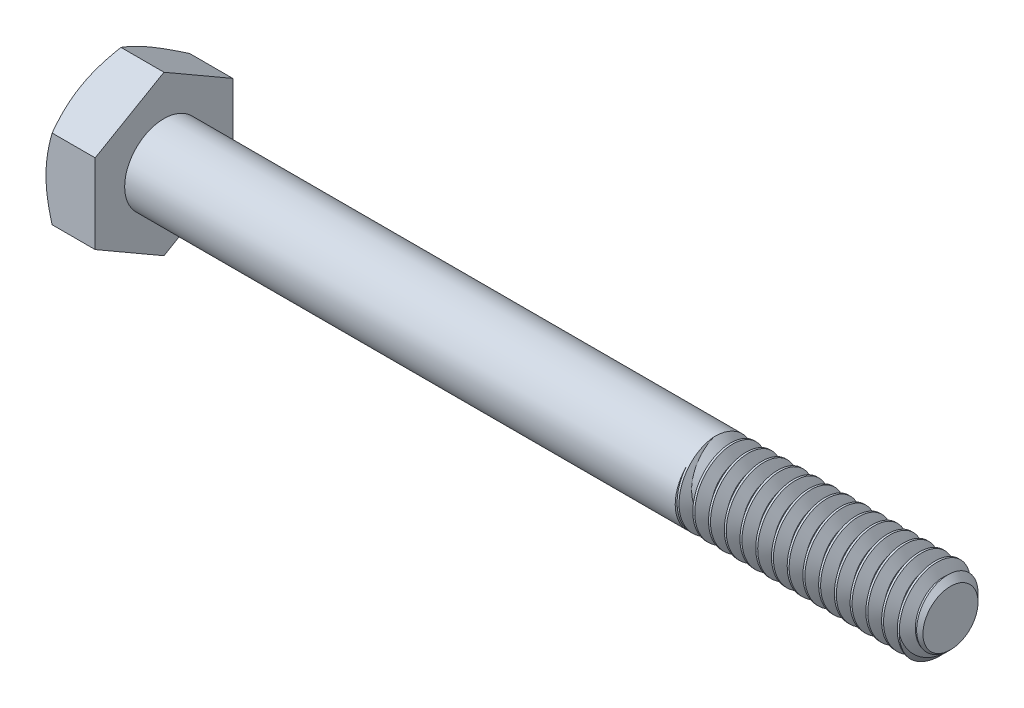
SolidWorks part; units mm, degrees
ref_plane "Front Plane" through (0, 0, 0) normal (0, 0, 1) x (1, 0, 0)
ref_plane "Top Plane" through (0, 0, 0) normal (0, 1, 0) x (1, 0, 0)
ref_plane "Right Plane" through (0, 0, 0) normal (1, 0, 0) x (0, 0, -1)
sketch "Sketch1" plane through (0, 0, 0) normal (0, 0, 1) x (1, 0, 0)
  line L0 (-33.7344, 0) -> (33.7344, 0) construction
  line L1 (33.7344, 3.175) -> (33.7344, -3.175) construction
  line L2 (-29.7656, 5.5563) -> (-29.7656, -5.5563) construction
  line L3 (-33.7344, 5.5562) -> (-33.7344, -5.5562) construction
  point P9 (-29.7656, 0)
  point P10 (29.2894, -3.175)
  dimension "Screw Dia" = 6.35
  dimension "Hex" = 11.1125
  dimension "Head Ht" = 3.9688
  dimension "Screw Lenght" = 63.5
  dimension "D1" = 4.445
ref_plane "Plane2" through (33.7344, 0, 0) normal (1, 0, 0) x (0, 0, -1)
sketch "Sketch5" plane through (33.7344, 0, 0) normal (1, 0, 0) x (0, 0, -1)
  circle A0 centre (0, 0) radius 3.175
extrude "Boss-Extrude3" add sketch "Sketch5" against normal up to vertex (63.5 mm away) up to point (-29.7656, 0, 0)
sketch "Sketch9" plane through (33.7344, 0, 0) normal (1, 0, 0) x (0, 0, -1)
  circle A1 centre (0, 0) radius 3.175
  circle A2 centre (0, 0) radius 3.175
  dimension "D1" = 0
curve "Helix/Spiral1" pitch 1.27 height 20.32 turns 16 parameters "Pitch"=1.27
chamfer "Chamfer1" distance 0.9525 angle 45 1 edges at (33.7344, 0, -3.175)
sketch "Sketch10" plane through (0, 0, 0) normal (0, 0, 1) x (1, 0, 0)
  line L0 (33.7344, 3.175) -> (34.2106, 2.3501)
  line L1 (34.2106, 2.3501) -> (34.3694, 2.3501)
  line L2 (34.3694, 2.3501) -> (34.8456, 3.175)
  line L3 (33.7344, 3.175) -> (34.8456, 3.175)
  line L4 (34.29, 3.175) -> (34.29, 2.3501) construction
  line L5 (33.9725, 2.7626) -> (34.6075, 2.7626) construction
  dimension "D1" = 60
  dimension "D2" = 0.1588
  dimension "D3" = 0.635
sweep "Cut-Sweep1" cut profiles "Sketch10" path "Helix/Spiral1" align with end faces yes
sketch "Sketch11" plane through (0, 0, 0) normal (0, 0, 1) x (1, 0, 0)
  line L0 (-29.7656, 3.175) -> (-29.7656, 0)
  line L1 (-29.7656, 0) -> (17.8594, 0)
  line L3 (17.8594, 0) -> (14.6844, 3.175)
  line L4 (-29.7656, 3.175) -> (14.6844, 3.175)
  dimension "D1" = 45
  dimension "MIn Thread" = 19.05
revolve "Revolve1" add sketch "Sketch11" angle 360 about L1
sketch "Sketch6" plane through (-29.7656, 0, 0) normal (-1, 0, 0) x (0, 0, 1)
  line L0 (0, 5.5563) -> (0, -5.5563) construction
  line L1 (5.5562, 3.2079) -> (0, 6.4158)
  line L2 (0, 6.4158) -> (-5.5562, 3.2079)
  line L3 (-5.5562, 3.2079) -> (-5.5562, -3.2079)
  line L4 (-5.5562, -3.2079) -> (0, -6.4158)
  line L5 (0, -6.4158) -> (5.5562, -3.2079)
  line L6 (5.5562, -3.2079) -> (5.5562, 3.2079)
  circle A0 centre (0, 0) radius 5.5563 construction
extrude "Boss-Extrude4" add sketch "Sketch6" along normal up to vertex (3.9688 mm away) up to point (-33.7344, -5.5562, 0)
sketch "Sketch7" plane through (-33.7344, 0, 0) normal (-1, 0, 0) x (0, 0, 1)
  circle A0 centre (0, 0) radius 5.5563 construction
  circle A1 centre (0, 0) radius 5.5563
sketch "Sketch8" plane through (-33.7344, 0, 0) normal (-1, 0, 0) x (0, 0, 1)
  circle A0 centre (0, 0) radius 5.5563 construction
  circle A1 centre (0, 0) radius 5.5563
extrude "Cut-Extrude3" cut sketch "Sketch8" against normal through all draft 60 flip side to cut
equation "\"D2@Sketch10\" = \"Pitch@Helix/Spiral1\"*.125"
equation "\"D3@Sketch10\" = \"Pitch@Helix/Spiral1\"*.5"
equation "\"D3@Helix/Spiral1\" = \"MIn Thread@Sketch11\"+\"Pitch@Helix/Spiral1\""
equation "\"D1@Chamfer1\" = \"Pitch@Helix/Spiral1\"*.75"
equation "\"D1@Sketch1\" = \"Pitch@Helix/Spiral1\"*3.5"
